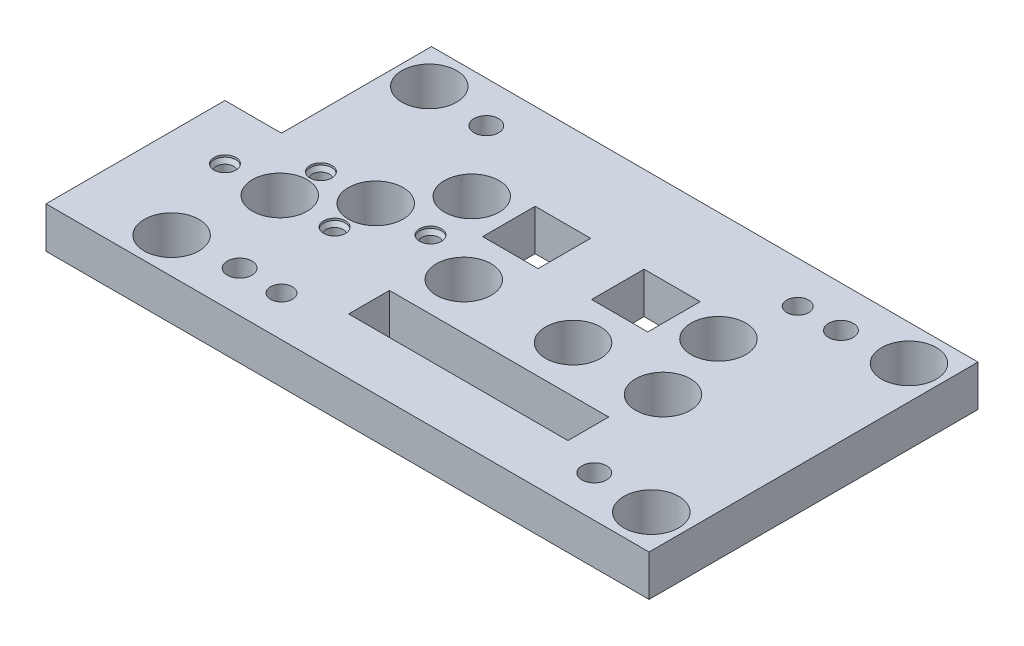
SolidWorks part; units mm, degrees
material "Plain Carbon Steel"
ref_plane "Front Plane" through (0, 0, 0) normal (0, 0, 1) x (1, 0, 0)
ref_plane "Top Plane" through (0, 0, 0) normal (0, 1, 0) x (1, 0, 0)
ref_plane "Right Plane" through (0, 0, 0) normal (1, 0, 0) x (0, 0, -1)
sketch "Sketch1" plane through (0, 0, 0) normal (0, 1, 0) x (1, 0, 0)
  line L1 (-110, -60) -> (110, -60)
  line L2 (-110, -60) -> (-110, 60)
  line L3 (-110, 60) -> (110, 60)
  line L4 (110, -60) -> (110, 60)
  line L5 (-110, -60) -> (110, 60) construction
  line L6 (-110, 60) -> (110, -60) construction
  point P0 (0, 0)
  dimension "D1" = 120
  dimension "D2" = 220
extrude "Boss-Extrude1" add sketch "Sketch1" against normal blind 15
sketch "Sketch2" plane through (0, 0, 0) normal (0, 1, 0) x (1, 0, 0)
  line L1 (-110, 60) -> (-89.3675, 60)
  line L2 (-110, 60) -> (-110, 5.27)
  line L3 (-110, 5.27) -> (-89.3675, 5.27)
  line L4 (-89.3675, 60) -> (-89.3675, 5.27)
  line L5 (-90, -14.72) -> (-89.3675, 5.27) construction
  line L10 (-70, 0.28) -> (-89.3675, 5.27) construction
  circle A0 centre (-70, 0.28) radius 3.1 construction
  circle A1 centre (-90, -14.72) radius 3.1 construction
  dimension "D1" = 20
extrude "Cut-Extrude1" cut sketch "Sketch2" against normal up to next
sketch "Sketch3" plane through (0, 0, 0) normal (0, 1, 0) x (1, 0, 0)
  line L0 (-20, 27.5) -> (-20, 9.28) construction
  line L1 (-20, 9.28) -> (0.25, 9.28) construction
  line L2 (0.25, 9.28) -> (0.25, 27.5) construction
  line L3 (19.75, 27.5) -> (19.75, 9.28) construction
  line L4 (19.75, 9.28) -> (40.25, 9.28) construction
  line L5 (40.25, 9.28) -> (40.25, 27.5) construction
  line L6 (-20, 28.44) -> (-20, 9.28)
  line L7 (-20, 9.28) -> (0.25, 9.28)
  line L8 (0.25, 9.28) -> (0.25, 28.44)
  line L9 (19.75, 28.44) -> (19.75, 9.28)
  line L10 (19.75, 9.28) -> (40.25, 9.28)
  line L11 (40.25, 9.28) -> (40.25, 28.44)
  line L12 (-20, 28.44) -> (0.25, 28.44)
  line L14 (19.75, 28.44) -> (40.25, 28.44)
  line L15 (0.31, 28.5) -> (-20.06, 28.5) construction
  dimension "D1" = 0.06
extrude "Cut-Extrude2" cut sketch "Sketch3" against normal up to next
sketch "Sketch4" plane through (0, 0, 0) normal (0, 1, 0) x (1, 0, 0)
  line L0 (-20.06, -39.66) -> (60.06, -39.66) construction
  line L1 (60, -24.72) -> (-20, -24.72)
  line L2 (60, -24.72) -> (60, -39.6)
  line L3 (60, -39.6) -> (-20, -39.6)
  line L4 (-20, -24.72) -> (-20, -39.6)
  dimension "D1" = 80
  dimension "D2" = 0.06
  dimension "D3" = 14.88
extrude "Cut-Extrude3" cut sketch "Sketch4" against normal up to next
hole_wizard "Ø6.2 (6.2) Diameter Hole1" positions "Sketch7" profile "Sketch6" hole size "Ø6.2" standard "ISO" end condition through all
sketch "Sketch7" plane through (0, 0, 0) normal (0, 1, 0) x (1, 0, 0)
  point P0 (-30, 0.28)
  point P3 (-50, -14.72)
  point P6 (-70, 0.28)
  point P9 (-90, -14.72)
sketch "Sketch6" plane through (-30, 0, -0.28) normal (1, 0, 0) x (0, 0, 1)
  line L0 (0, 0) -> (0, 15)
  line L1 (0, 15) -> (3.1, 15)
  line L2 (3.1, 15) -> (3.1, 0)
  line L5 (3.1, 0) -> (0, 0)
  line L11 (0, -6.35) -> (0, 107.95) construction
  dimension "Thru Hole Dia." = 6.2
  dimension "Thru Hole Depth" = 15
sketch "Sketch8" plane through (0, 0, 0) normal (0, 1, 0) x (1, 0, 0)
  circle A0 centre (-90, -14.72) radius 4
  circle A1 centre (-70, 0.28) radius 4
  circle A2 centre (-50, -14.72) radius 4
  circle A3 centre (-30, 0.28) radius 4
  dimension "D1" = 8
extrude "Cut-Extrude4" cut sketch "Sketch8" against normal blind 0.5
chamfer "Chamfer1" distance 1.8 angle 30 4 edges at (-90, -0.5, 17.82) (-30, -0.5, 2.82) (-50, -0.5, 17.82) (-70, -0.5, 2.82) first distance on face at (-90, -15, 17.82) first distance on face at (-30, -15, 2.82) first distance on face at (-50, -15, 17.82) first distance on face at (-70, -15, 2.82)
sketch "Sketch9" plane through (0, 0, 0) normal (0, 1, 0) x (1, 0, 0)
  circle A0 centre (-77.1837, -47) radius 10 construction
  circle A1 centre (97.8163, -47) radius 10 construction
  circle A2 centre (62.8163, -7.72) radius 10 construction
  circle A3 centre (30, -7.72) radius 10 construction
  circle A4 centre (-9.875, -7.72) radius 10 construction
  circle A5 centre (-70, -14.72) radius 10 construction
  circle A6 centre (-50, 0.28) radius 10 construction
  circle A7 centre (55.3163, 20) radius 10 construction
  circle A8 centre (97.8163, 47) radius 10 construction
  circle A12 centre (-34.6837, 20) radius 10 construction
  circle A13 centre (-77.1837, 47) radius 10 construction
  circle A14 centre (-77.1837, -47) radius 10
  circle A15 centre (97.8163, -47) radius 10
  circle A16 centre (62.8163, -7.72) radius 10
  circle A17 centre (30, -7.72) radius 10
  circle A18 centre (-9.875, -7.72) radius 10
  circle A19 centre (-70, -14.72) radius 10
  circle A20 centre (-50, 0.28) radius 10
  circle A21 centre (55.3163, 20) radius 10
  circle A22 centre (97.8163, 47) radius 10
  circle A26 centre (-34.6837, 20) radius 10
  circle A27 centre (-77.1837, 47) radius 10
extrude "Cut-Extrude5" cut sketch "Sketch9" against normal up to next
hole_wizard "CBORE for M8 Hex Socket Head Cap Screw1" positions "Sketch17" profile "Sketch11" counterbore size "M8" standard "ISO" end condition through all
sketch "Sketch17" plane through (0, -15, 0) normal (0, -1, 0) x (-1, 0, 0)
  line L0 (-110, -60) -> (-110, 60) construction
  line L1 (-110, 60) -> (89.3675, 60) construction
  line L3 (89.3675, 5.27) -> (89.3675, 60) construction
  line L4 (110, -60) -> (-110, -60) construction
  point P4 (-75, 45)
  point P6 (54.3675, 45)
  point P8 (54.3675, -45)
  point P10 (-75, -45)
  dimension "D1" = 35
  dimension "D2" = 15
  dimension "D3" = 35
  dimension "D4" = 15
sketch "Sketch11" plane through (75, -15, -45) normal (1, 0, 0) x (0, 0, -1)
  line L0 (0, 0) -> (0, 15)
  line L1 (0, 15) -> (4.5, 15)
  line L3 (4.5, 15) -> (4.5, 8.6)
  line L4 (4.5, 8.6) -> (7.5, 8.6)
  line L5 (7.5, 8.6) -> (7.5, 0)
  line L7 (7.5, 0) -> (0, 0)
  line L11 (0, -6.35) -> (0, 107.95) construction
  dimension "Thru Hole Dia." = 9
  dimension "Thru Hole Depth" = 15
  dimension "C'Bore Dia." = 15
  dimension "C'Bore Depth" = 8.6
hole_wizard "Ø8.0mm Dowel Hole1" positions "Sketch15" profile "Sketch14" hole size "Ø8.0" standard "ISO" end condition through all
sketch "Sketch15" plane through (0, -15, 0) normal (0, -1, 0) x (-1, 0, 0)
  circle A0 centre (-75, 45) radius 7.5 construction
  circle A1 centre (54.3675, -45) radius 7.5 construction
  point P0 (-59.5, 44.7284)
  point P4 (38.8675, -45.241)
  dimension "D1" = 8
  dimension "D2" = 8
sketch "Sketch14" plane through (59.5, -15, -44.7284) normal (1, 0, 0) x (0, 0, -1)
  line L0 (0, 0) -> (0, 15)
  line L1 (0, 15) -> (4, 15)
  line L2 (4, 15) -> (4, 0)
  line L5 (4, 0) -> (0, 0)
  line L11 (0, -6.35) -> (0, 107.95) construction
  dimension "Thru Hole Dia." = 8
  dimension "Thru Hole Depth" = 15
